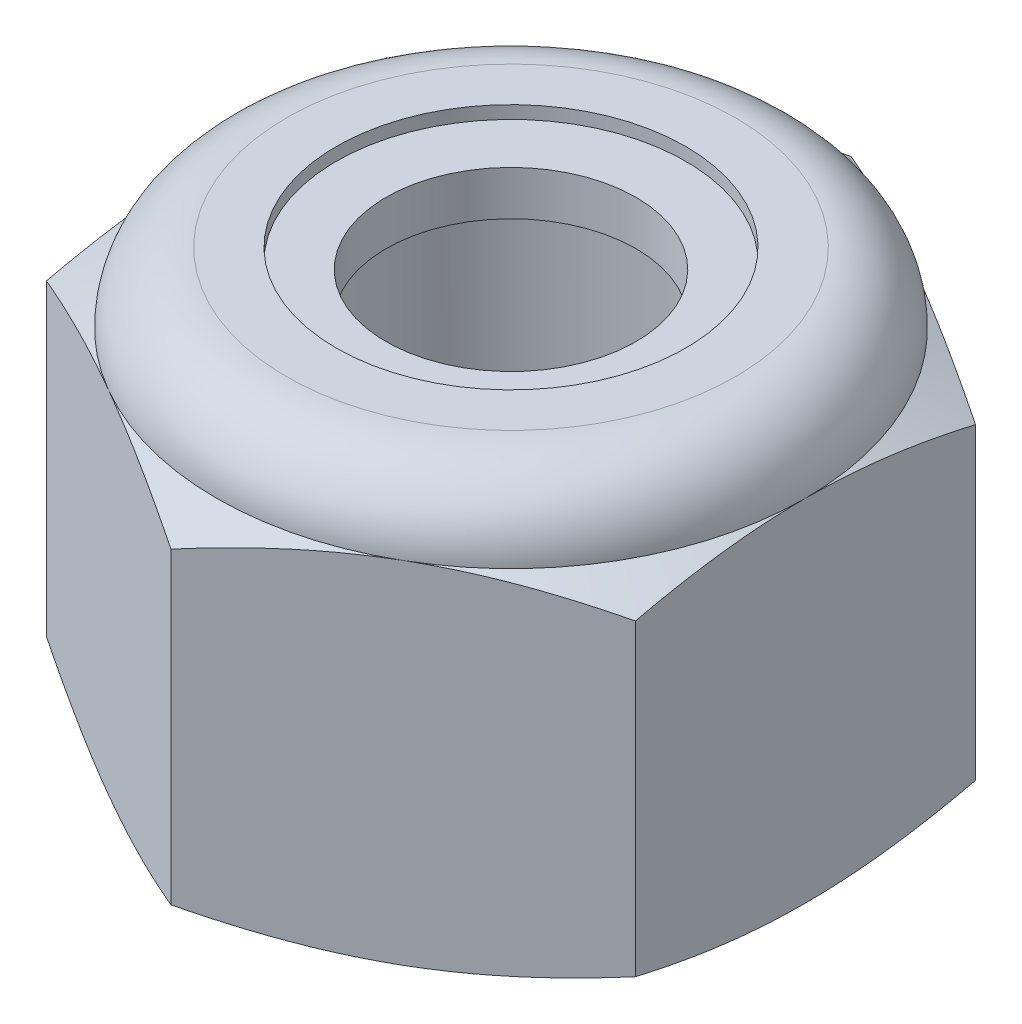
SolidWorks part; units mm, degrees
material "Alloy Steel"
ref_plane "Front" through (0, 0, 0) normal (0, 0, 1) x (1, 0, 0)
ref_plane "Top" through (0, 0, 0) normal (0, 1, 0) x (1, 0, 0)
ref_plane "Right" through (0, 0, 0) normal (1, 0, 0) x (0, 0, -1)
sketch "Sketch1" plane through (0, 0, 0) normal (0, 1, 0) x (1, 0, 0)
  line L0 (0, 0) -> (1.4142, -1.4142) construction
  line L1 (0, 4.0415) -> (-3.5, 2.0207)
  line L2 (-3.5, 2.0207) -> (-3.5, -2.0207)
  line L3 (-3.5, -2.0207) -> (0, -4.0415)
  line L4 (0, -4.0415) -> (3.5, -2.0207)
  line L5 (3.5, -2.0207) -> (3.5, 2.0207)
  line L6 (3.5, 2.0207) -> (0, 4.0415)
  circle A0 centre (0, 0) radius 3.5 construction
  circle A1 centre (0, 0) radius 2
  point P12 (1.4142, -1.4142)
  dimension "Thread Dia" = 4
  dimension "Hex Flats" = 7
  dimension "D1" = 45
extrude "Extrude1" add sketch "Sketch1" along normal blind 5
chamfer "Chamfer1" distance 0.2 angle 45 1 edges at (0, 0, 2)
sketch "Sketch5" plane through (0, 0, 0) normal (1, 0, 0) x (0, 0, -1)
  line L0 (0, 0) -> (3.5, 0)
  line L1 (3.5, 0) -> (4.0415, 0.2525)
  line L2 (4.0415, 0.2525) -> (4.0415, 3.9142)
  line L3 (4.0415, 3.9142) -> (3.5, 4.1667)
  line L4 (2.6667, 5) -> (2.6667, 6.27)
  line L5 (2.6667, 6.27) -> (5.3115, 6.27)
  line L6 (5.3115, 6.27) -> (5.3115, -1.27)
  line L7 (5.3115, -1.27) -> (0, -1.27)
  line L8 (0, -1.27) -> (0, 0)
  line L9 (3.5, 4.1667) -> (3.5, 0) construction
  line L10 (2.0207, 5) -> (4.0415, 5) construction
  line L13 (4.0415, 2.0833) -> (5.3115, 2.0833) construction
  line L14 (4.0415, 5) -> (4.0415, 0) construction
  line L15 (0, 0) -> (0, 6.27) construction
  line L20 (0, 6.27) -> (2.6667, 6.27) construction
  arc A0 (3.5, 4.1667) -> (2.6667, 5) centre (2.6667, 4.1667) ccw
  dimension "D1" = 25
  dimension "D2" = 1.27
  dimension "D3" = 5
  dimension "D4" = 0.8333
revolve "Cut-Revolve3" cut sketch "Sketch5" angle 360 about L15
sketch "Sketch6" plane through (0, 0, 0) normal (1, 0, 0) x (0, 0, -1)
  line L0 (0, 4.1667) -> (3.3476, 4.1667)
  line L1 (2.6667, 4.8476) -> (2.0762, 4.8476)
  line L2 (0, 6.27) -> (0, 4.1667)
  line L3 (2.0762, 6.27) -> (0, 6.27)
  line L4 (0, 6.27) -> (2.6667, 6.27) construction
  line L5 (0, 0) -> (0, 6.27) construction
  line L6 (0, 6.27) -> (0, 0) construction
  line L7 (2.0762, 4.8476) -> (2.0762, 6.27)
  line L8 (2.6667, 5) -> (2.6667, 4.8476) construction
  line L9 (2.0762, 4.8476) -> (1.9238, 4.8476) construction
  line L21 (2, 4.8476) -> (2, 5) construction
  arc A0 (3.3476, 4.1667) -> (2.6667, 4.8476) centre (2.6667, 4.1667) ccw
  arc A1 (3.5, 4.1667) -> (2.6667, 5) centre (2.6667, 4.1667) ccw construction
  dimension "D1" = 0.1524
revolve "Cut-Revolve4" cut sketch "Sketch6" angle 360 about L6
sketch "Sketch7" plane through (0, 0, 0) normal (1, 0, 0) x (0, 0, -1)
  line L0 (1.4857, 4.2429) -> (3.2666, 4.2429)
  line L1 (2.6667, 4.7714) -> (1.4857, 4.7714)
  line L2 (1.4857, 4.7714) -> (1.4857, 4.2429)
  line L3 (1.4857, 4.2429) -> (0, 4.2429) construction
  line L4 (0, 4.2429) -> (0, 4.7714) construction
  line L5 (0, 4.7714) -> (1.4857, 4.7714) construction
  line L6 (1.4857, 4.2429) -> (1.4857, 4.1667) construction
  line L7 (0, 4.1667) -> (3.3476, 4.1667) construction
  line L8 (2.6667, 4.7714) -> (2.6667, 4.8476) construction
  line L10 (1.4857, 4.8476) -> (2.0762, 4.8476) construction
  line L11 (2.6667, 4.8476) -> (2.0762, 4.8476) construction
  arc A0 (3.2666, 4.2429) -> (2.6667, 4.7714) centre (2.6667, 4.1667) ccw
  arc A2 (3.3476, 4.1667) -> (2.6667, 4.8476) centre (2.6667, 4.1667) ccw construction
  dimension "D1" = 0.0762
revolve "Revolve2" add sketch "Sketch7" angle 360 about L4
ref_axis "Center Axis 1" [suppressed] through (0, 4.1667, 0) along (0, -1, 0)
sketch "Sketch12" [suppressed] plane through (0, 0, 0) normal (0, -1, 0) x (1, 0, 0)
  circle A0 centre (0, 0) radius 2
  circle A1 centre (0, 0) radius 2 construction
extrude "Boss-Extrude3" [suppressed] add sketch "Sketch12" against normal up to vertex up to point (0, 4.1667, -3.3476)
sketch "Sketch2" [suppressed] plane through (0, 0, 0) normal (1, 0, 0) x (0, 0, -1)
  line L1 (0, 0) -> (2, 0)
  line L2 (0, 0) -> (0, 4.8476)
  line L3 (0, 4.8476) -> (2, 4.8476)
  line L4 (2, 0) -> (2, 4.8476)
  line L7 (0, -2) -> (0, 0) construction
  line L11 (2.6667, 4.8476) -> (2.0762, 4.8476) construction
revolve "Revolve1" [suppressed] add sketch "Sketch2" angle 360 about L7
sketch "Sketch8" [suppressed] plane through (0, 0, 0) normal (0, -1, 0) x (1, 0, 0)
  circle A0 centre (0, 0) radius 2 construction
  circle A2 centre (0, 0) radius 2
curve "Helix/Spiral1" [suppressed] pitch 0.7 height 10 turns 14.2857 parameters "Pitch"=0.7
sketch "Sketch9" [suppressed] plane through (0, 0, 0) normal (1, 0, 0) x (0, 0, -1)
  line L0 (2, -0.6125) -> (2, 0)
  line L1 (2, -0.6125) -> (1.5453, -0.35)
  line L2 (1.5453, -0.35) -> (1.5453, -0.2625)
  line L3 (1.5453, -0.2625) -> (2, 0)
  line L4 (-2, 0) -> (2, 0) construction
  line L5 (2, -0.3062) -> (1.5453, -0.3062) construction
  line L6 (1.7727, -0.4812) -> (1.7727, -0.1312) construction
  dimension "D1" = 0.0875
  dimension "D2" = 0.35
  dimension "D3" = 60
sweep "Cut-Sweep1" [suppressed] cut profiles "Sketch9" path "Helix/Spiral1"
combine bodies "Combine1" [suppressed] operation type subtract main body 135 bodies to subtract 132
sketch "Sketch14" [suppressed] plane through (0, 0, 0) normal (1, 0, 0) x (0, 0, -1)
  line L0 (0, 0) -> (0, 5) construction
  line L1 (2.0762, 5) -> (-2.0762, 5) construction
  line L2 (-2.2, 0) -> (-1, 1.2)
  line L4 (-2, 0) -> (-2.2, 0)
  line L9 (-1, 1.2) -> (0, 1.2)
  line L10 (0, 1.2) -> (0, 0)
  line L11 (0, 0) -> (-2, 0)
  line L12 (-1, 1.2) -> (-1, 0) construction
  dimension "D1" = 45
  dimension "D2" = 4
  dimension "D3" = 0.2
revolve "Cut-Revolve5" [suppressed] cut sketch "Sketch14" angle 360 about L0
equation "\"D4@Sketch5\"=\"Height@Extrude1\"/6"
equation "\"D3@Helix/Spiral1\"=2*\"Height@Extrude1\""
equation "\"D1@Sketch9\"=\"Pitch@Helix/Spiral1\"*.125"
equation "\"D2@Sketch9\"=\"Pitch@Helix/Spiral1\"*.50"
equation "\"D1@Chamfer1\"=.05*\"Thread Dia@Sketch1\""
equation "\"D2@Sketch14\"=\"Thread Dia@Sketch1\""
equation "\"D3@Sketch14\"=\"D1@Chamfer1\""
